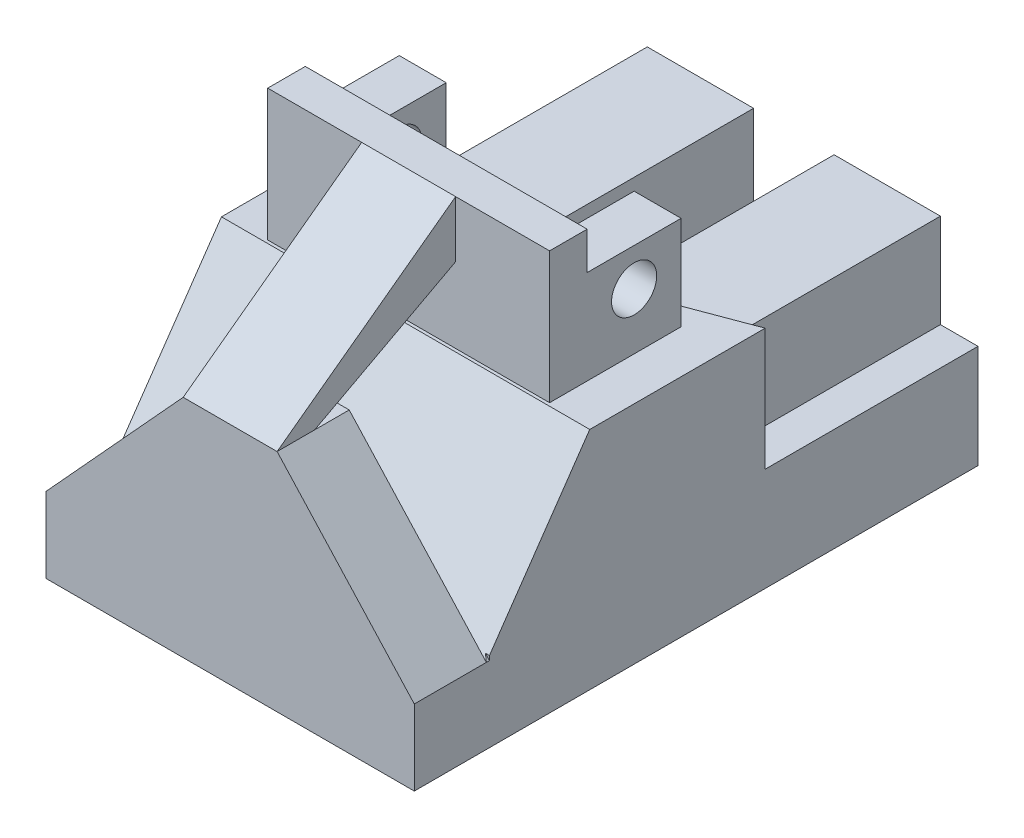
SolidWorks part; units mm, degrees
material "ABS"
ref_plane "Front Plane" through (0, 0, 0) normal (0, 0, 1) x (1, 0, 0)
ref_plane "Top Plane" through (0, 0, 0) normal (0, 1, 0) x (1, 0, 0)
ref_plane "Right Plane" through (0, 0, 0) normal (1, 0, 0) x (0, 0, -1)
sketch "Sketch2" plane through (0, 0, 0) normal (1, 0, 0) x (0, 0, -1)
  line L0 (0, 0) -> (0, 12)
  line L1 (0, 12) -> (30, 12)
  line L2 (30, 12) -> (30, 0)
  line L3 (30, 0) -> (0, 0)
extrude "Boss-Extrude2" add sketch "Sketch2" along normal blind 10 and the other way blind 10 contours L1 L2 L3 L0
sketch "Sketch5" plane through (0, 12, 0) normal (0, 1, 0) x (1, 0, 0)
  line L2 (-10, 18.75) -> (-10, 30)
  line L3 (-10, 0) -> (-10, 30) construction
  line L4 (-10, 30) -> (10, 30)
  line L5 (10, 0) -> (10, 30) construction
  line L6 (10, 18.75) -> (0, 15)
  line L7 (-10, 18.75) -> (0, 15)
  line L8 (10, 30) -> (10, 18.75)
ref_plane "Plane1" through (0, 0, 0) normal (-1, 0, 0) x (0, 0, 1)
sketch "Sketch11" plane through (0, 12, 0) normal (0, 1, 0) x (1, 0, 0)
  line L0 (-5, 16.5) -> (-5, 11.5)
  line L5 (-5, 11.5) -> (-7.5, 11.5)
  line L6 (-7.5, 11.5) -> (-7.5, 16.5)
  line L7 (-7.5, 16.5) -> (-5, 16.5)
extrude "Boss-Extrude5" add sketch "Sketch11" along normal blind 5 contours L5 L6 L7 L0
sketch "Sketch12" plane through (-5, 0, 0) normal (1, 0, 0) x (0, 0, -1)
  circle A0 centre (14, 15) radius 1.2
extrude "Cut-Extrude3" cut sketch "Sketch12" against normal blind 5 contours A0
mirror "Mirror2" about plane through (0, 0, 0) normal (-1, 0, 0) of "Cut-Extrude3", "Boss-Extrude5"
sketch "Sketch13" plane through (0, 12, 0) normal (0, 1, 0) x (1, 0, 0)
  line L0 (-7.5, 11.5) -> (-7.5, 9.5)
  line L1 (7.5, 11.5) -> (7.5, 9.5)
  line L2 (7.5, 9.5) -> (-7.5, 9.5)
  line L3 (-7.5, 11.5) -> (7.5, 11.5)
extrude "Boss-Extrude6" add sketch "Sketch13" along normal blind 7 contours L2 L0 L3 L1
sketch "Sketch16" plane through (10, 0, 0) normal (1, 0, 0) x (0, 0, -1)
  line L1 (0, 12) -> (30, 12)
  line L2 (0, 12) -> (0, 0)
  line L3 (0, 0) -> (30, 0)
  line L4 (30, 12) -> (30, 0)
extrude "Cut-Extrude4" cut sketch "Sketch16" against normal blind 0.2 contours L4 L3 L2 L1
mirror "Mirror3" about plane through (0, 0, 0) normal (-1, 0, 0) of "Cut-Extrude4"
extrude "Cut-Extrude5" cut sketch "Sketch5" against normal blind 1.5 contours L2 L4 L8 L6 L7
sketch "Sketch19" plane through (0, 0, -9.5) normal (0, 0, 1) x (1, 0, 0)
  line L0 (0, 55) -> (0, -55) construction
  line L1 (2.5, 16) -> (-2.5, 16)
  line L2 (2.5, 16) -> (2.5, 19)
  line L3 (2.5, 19) -> (-2.5, 19)
  line L4 (-2.5, 16) -> (-2.5, 19)
  line L5 (2.5, 16) -> (-2.5, 19) construction
  line L6 (2.5, 19) -> (-2.5, 16) construction
  line L7 (7.5, 19) -> (-7.5, 19) construction
  point P0 (0, 17.5)
sketch "Sketch20" plane through (0, 12, 0) normal (0, 1, 0) x (1, 0, 0)
  line L0 (0, 55) -> (0, -55) construction
  line L1 (-2.5, 2) -> (2.5, 2)
  line L2 (-2.5, 2) -> (-2.5, 0)
  line L3 (-2.5, 0) -> (2.5, 0)
  line L4 (2.5, 2) -> (2.5, 0)
  line L5 (-2.5, 2) -> (2.5, 0) construction
  line L6 (-2.5, 0) -> (2.5, 2) construction
  line L7 (-9.8, 0) -> (9.8, 0) construction
  point P0 (0, 1)
loft "Loft1" add profiles "Sketch20", "Sketch19" connector at (-2.5, 12, -2) connector at (-2.5, 16, -9.5)
sketch "Sketch22" plane through (-9.8, 0, 0) normal (-1, 0, 0) x (0, 0, 1)
  line L0 (-9.3375, 12) -> (-3.8365, 4.0148)
  line L1 (0, 12) -> (-18.675, 12) construction
  line L2 (-3.8365, 4.0148) -> (-3.8365, 12)
  line L3 (-3.8365, 12) -> (-9.3375, 12)
extrude "Cut-Extrude6" cut sketch "Sketch22" against normal blind 31 contours L2 L3 L0
sketch "Sketch23" plane through (0, 10.5, 0) normal (0, 1, 0) x (1, 0, 0)
  line L0 (-2.1418, 15.8032) -> (-2.1418, 30)
  line L1 (-9.8, 18.675) -> (0, 15) construction
  line L2 (-9.8, 30) -> (9.8, 30) construction
  line L3 (-2.1418, 15.8032) -> (2.1418, 15.8032)
  line L4 (9.8, 18.675) -> (0, 15) construction
  line L5 (2.1418, 15.8032) -> (2.1418, 30)
  line L6 (2.1418, 30) -> (-2.1418, 30)
extrude "Cut-Extrude7" cut sketch "Sketch23" against normal blind 5 contours L0 L6 L5 L3
sketch "Sketch24" plane through (0, 10.5, 0) normal (0, 1, 0) x (1, 0, 0)
  line L0 (9.8, 30) -> (9.8, 18.675)
  line L1 (9.8, 18.675) -> (7.8, 18.675)
  line L2 (7.8, 18.675) -> (7.8, 30)
  line L3 (2.1418, 30) -> (9.8, 30) construction
  line L4 (7.8, 30) -> (9.8, 30)
extrude "Cut-Extrude8" cut sketch "Sketch24" against normal blind 5 contours L2 L4 L0 L1
mirror "Mirror4" about plane through (0, 0, 0) normal (-1, 0, 0) of "Cut-Extrude8"
sketch "Sketch25" plane through (0, 0, 0) normal (0, 0, 1) x (1, 0, 0)
  line L0 (-9.8, 12) -> (-9.8, 4.0148)
  line L1 (-9.8, 4.0148) -> (-2.5, 12)
  line L2 (7.5, 12) -> (-7.5, 12) construction
  line L3 (-2.5, 12) -> (2.5, 12) construction
  line L4 (-2.5, 12) -> (-9.8, 12)
extrude "Cut-Extrude9" cut sketch "Sketch25" against normal blind 4 contours L1 L4 L0
mirror "Mirror5" about plane through (0, 0, 0) normal (-1, 0, 0) of "Cut-Extrude9"
